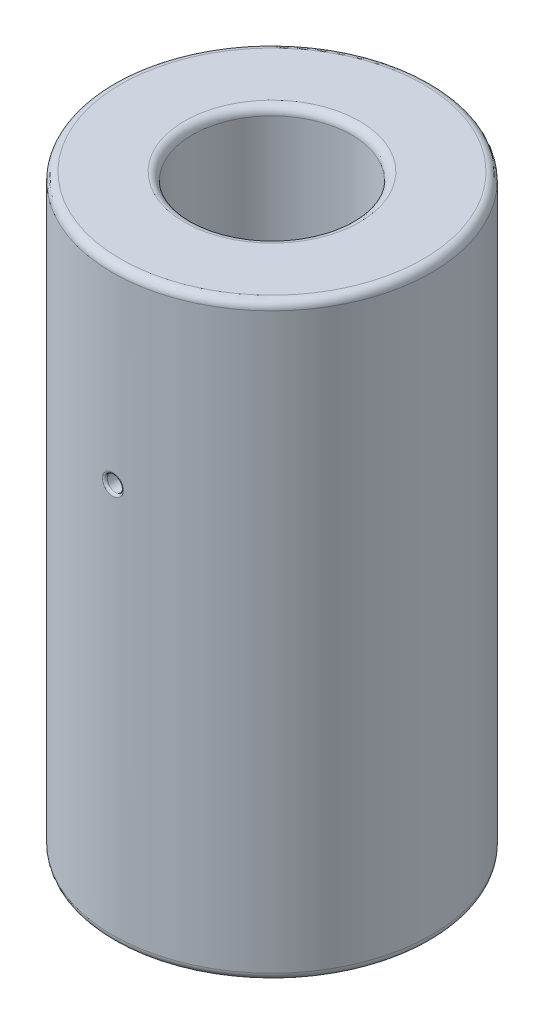
SolidWorks part; units mm, degrees
ref_plane "Front Plane" through (0, 0, 0) normal (0, 0, 1) x (1, 0, 0)
ref_plane "Top Plane" through (0, 0, 0) normal (0, 1, 0) x (1, 0, 0)
ref_plane "Right Plane" through (0, 0, 0) normal (1, 0, 0) x (0, 0, -1)
sketch "Sketch1" plane through (0, 0, 0) normal (0, 1, 0) x (1, 0, 0)
  circle A0 centre (0, 0) radius 20
  dimension "D1" = 40
extrude "Boss-Extrude1" add sketch "Sketch1" along normal blind 74
sketch "Sketch2" plane through (0, 74, 0) normal (0, 1, 0) x (1, 0, 0)
  circle A0 centre (0, 0) radius 10
  dimension "D1" = 20
extrude "Cut-Extrude3" cut sketch "Sketch2" against normal blind 20
sketch "Sketch3" plane through (0, 0, 0) normal (0, 0, 1) x (1, 0, 0)
  line L0 (0, 0) -> (0, 50) construction
  circle A0 centre (0, 50) radius 1
  dimension "D1" = 2
  dimension "D2" = 50
extrude "Cut-Extrude1" cut sketch "Sketch3" against normal through all and the other way through all contours A0
sketch "Sketch5" plane through (0, 0, 0) normal (1, 0, 0) x (0, 0, -1)
  line L0 (0, 0) -> (0, 20) construction
  circle A0 centre (0, 20) radius 1
  spline S0 degree 2 poles (-20, 51) (-19.95, 50) (-20, 49) knots 0 0 0 1 1 1 weights 0.019 0.02 0.021 construction
  spline S1 degree 2 poles (-20, 51) (-19.95, 50) (-20, 49) knots 0 0 0 1 1 1 weights 0.019 0.02 0.021 construction
  dimension "D1" = 2
  dimension "D2" = 20
extrude "Cut-Extrude2" cut sketch "Sketch5" against normal through all
fillet "Fillet2" radius 1 4 edges at (0, 0, 20) (0, 74, 20) (0, 74, 10) (0, 54, 10)
fillet "Fillet3" radius 0.3 3 edges at (0.2286, 49.0265, -19.9987) (-0.9735, 50.2286, 19.9763) (-19.9987, 20.9735, 0.2286)
ref_axis "x" through (0, 50, -19.7566) along (0, 0, 1)
ref_axis "Axis2" through (-19.7566, 20, 0) along (1, 0, 0)
ref_plane "Plane1" through (0, 50, 0) normal (0, 1, 0) x (1, 0, 0)
sketch "Sketch8" plane through (0, 50, 0) normal (0, 1, 0) x (1, 0, 0)
  circle A0 centre (0, 0) radius 11 construction
ref_plane "Plane2" through (-20, 0, 0) normal (-1, 0, 0) x (0, 0, 1)
sketch "Sketch10" plane through (-20, 0, 0) normal (-1, 0, 0) x (0, 0, 1)
  circle A0 centre (0, 20) radius 1 construction
ref_axis "k" through (0, 50, 0) along (-0.5547, -0.8321, 0)
ref_plane "Plane3" through (-23.0769, 15.3846, 0) normal (0.8321, -0.5547, 0) x (0, 0, -1)
sketch "Sketch11" plane through (0, 50, 0) normal (0, 1, 0) x (1, 0, 0)
  line L0 (19, 0) -> (-19, 0) construction
  line L1 (-19.7566, 0) -> (0, 0) construction
  circle A0 centre (0, 0) radius 19 construction
ref_axis "y-natural" through (19, 50, 0) along (-1, 0, 0)
sketch "Sketch12" plane through (-20, 0, 0) normal (-1, 0, 0) x (0, 0, 1)
  line L0 (0, 0) -> (0, 74) construction
  line L1 (11, 74) -> (-11, 74) construction
ref_axis "z-natural" through (-20, 0, 0) along (0, 1, 0)
